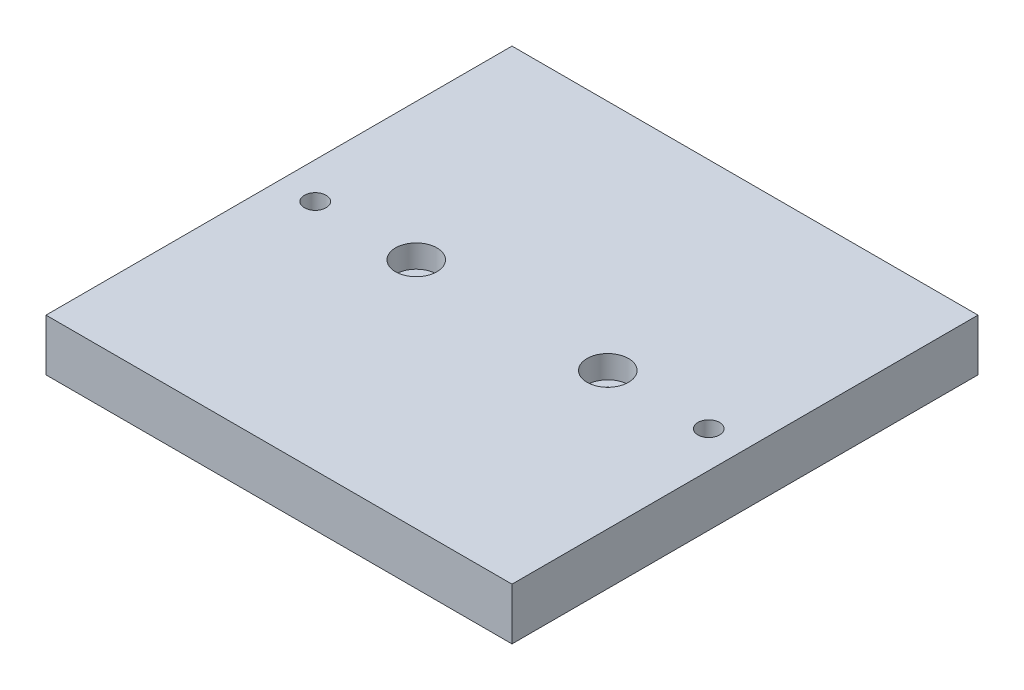
SolidWorks part; units mm, degrees
ref_plane "Front Plane" through (0, 0, 0) normal (0, 0, 1) x (1, 0, 0)
ref_plane "Top Plane" through (0, 0, 0) normal (0, 1, 0) x (1, 0, 0)
ref_plane "Right Plane" through (0, 0, 0) normal (1, 0, 0) x (0, 0, -1)
sketch "Sketch1" plane through (0, 0, 0) normal (0, 1, 0) x (1, 0, 0)
  line L1 (-105.4601, 36.8558) -> (-15.4601, 36.8558)
  line L2 (-105.4601, 36.8558) -> (-105.4601, -53.1442)
  line L3 (-105.4601, -53.1442) -> (-15.4601, -53.1442)
  line L4 (-15.4601, 36.8558) -> (-15.4601, -53.1442)
  dimension "D1" = 90
  dimension "D2" = 90
extrude "Boss-Extrude1" add sketch "Sketch1" along normal blind 10
sketch "Sketch2" plane through (0, 10, 0) normal (0, 1, 0) x (1, 0, 0)
  line L0 (-15.4601, 36.8558) -> (-105.4601, 36.8558) construction
  line L1 (-105.4601, 36.8558) -> (-105.4601, -53.1442) construction
  line L2 (-15.4601, -53.1442) -> (-15.4601, 36.8558) construction
  circle A0 centre (-78.9601, -8.1442) radius 4
  circle A1 centre (-41.9601, -8.1442) radius 4
  circle A2 centre (-78.9601, -8.1442) radius 2.25
  circle A3 centre (-41.9601, -8.1442) radius 2.25
  point P12 (-98.4601, -8.1442)
  point P13 (-22.4601, -8.1442)
  dimension "D2" = 8
  dimension "D3" = 8
  dimension "D6" = 4.5
  dimension "D7" = 4.5
  dimension "D8" = 26.5
  dimension "D1" = 37
  dimension "D4" = 45
  dimension "D5" = 26.5
  dimension "D9" = 45
  dimension "D10" = 7
  dimension "D11" = 45
  dimension "D12" = 7
extrude "Cut-Extrude1" cut sketch "Sketch2" against normal blind 74 and the other way blind 95 contours A2 | A3
extrude "Cut-Extrude2" cut sketch "Sketch2<3>" against normal blind 4.4
sketch "Sketch2<3>" plane through (0, 10, 0) normal (0, 1, 0) x (1, 0, 0) same geometry as "Sketch2"
hole_wizard "M5 Tapped Hole1" positions "Sketch3" profile "Sketch6" tap size "M5" standard "ISO" end condition through all
sketch "Sketch3" plane through (0, 10, 0) normal (0, 1, 0) x (1, 0, 0)
  point P0 (-98.4601, -8.1442)
  point P3 (-22.4601, -8.1442)
cosmetic thread "Hole Thread1" parameters "D2"=5
cosmetic thread "Hole Thread2" parameters "D2"=5
sketch "Sketch6" plane through (-98.4601, 10, 8.1442) normal (1, 0, 0) x (0, 0, 1)
  line L0 (0, 0) -> (0, 10)
  line L1 (0, 10) -> (2.1, 10)
  line L2 (2.1, 10) -> (2.1, 0)
  line L5 (2.1, 0) -> (0, 0)
  line L11 (0, -6.35) -> (0, 107.95) construction
  dimension "Thru Tap Drill Dia." = 4.2
  dimension "Thru Tap Drill Depth" = 10
